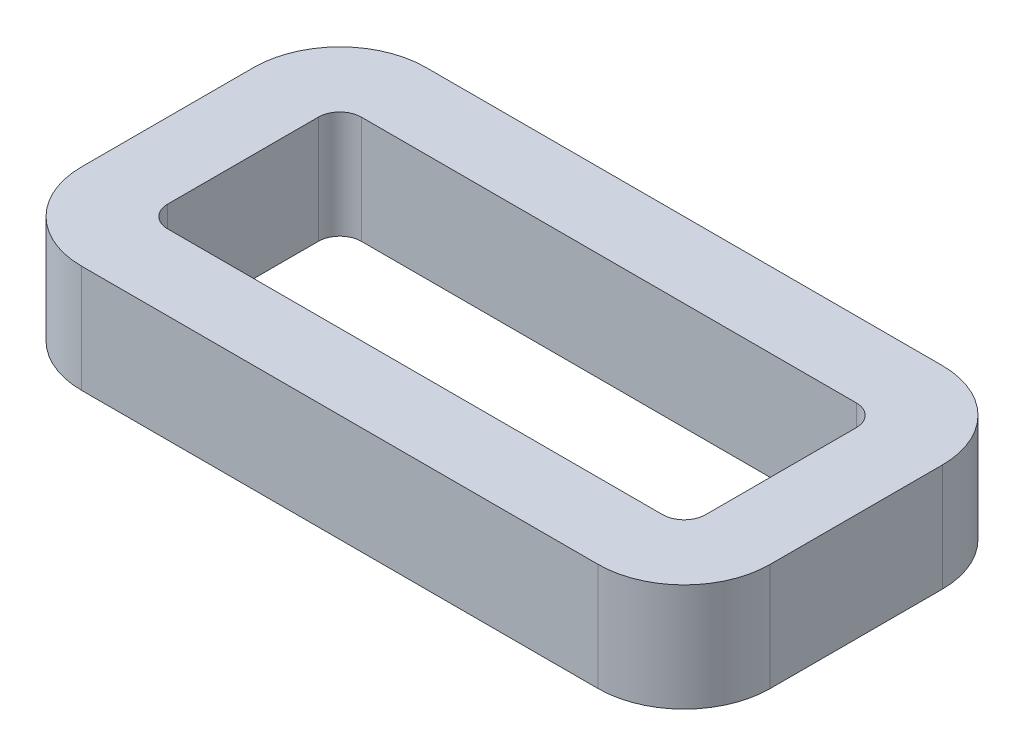
SolidWorks part; units mm, degrees
ref_plane "Alzado" through (0, 0, 0) normal (0, 0, 1) x (1, 0, 0)
ref_plane "Planta" through (0, 0, 0) normal (0, 1, 0) x (1, 0, 0)
ref_plane "Vista lateral" through (0, 0, 0) normal (1, 0, 0) x (0, 0, -1)
sketch "Croquis1" plane through (0, 0, 0) normal (0, 1, 0) x (1, 0, 0)
  line L0 (8, 0) -> (8, 1.75) construction
  line L1 (2, 0) -> (14, 0)
  line L2 (0, 2) -> (0, 6)
  line L3 (2, 8) -> (14, 8)
  line L4 (16, 2) -> (16, 6)
  line L5 (0, 4) -> (1.75, 4) construction
  line L6 (8, 8) -> (8, 6.25) construction
  line L7 (16, 4) -> (14.25, 4) construction
  line L8 (8, 6.25) -> (1.75, 6.25) construction
  line L9 (1.75, 5.75) -> (1.75, 2.25)
  line L10 (2.25, 1.75) -> (13.75, 1.75)
  line L11 (14.25, 2.25) -> (14.25, 5.75)
  line L12 (14.25, 6.25) -> (8, 6.25) construction
  line L13 (2.25, 6.25) -> (13.75, 6.25)
  arc A0 (1.75, 5.75) -> (2.25, 6.25) centre (2.25, 5.75) cw
  arc A1 (13.75, 6.25) -> (14.25, 5.75) centre (13.75, 5.75) cw
  arc A2 (14.25, 2.25) -> (13.75, 1.75) centre (13.75, 2.25) cw
  arc A3 (1.75, 2.25) -> (2.25, 1.75) centre (2.25, 2.25) ccw
  arc A4 (0, 6) -> (2, 8) centre (2, 6) cw
  arc A5 (2, 0) -> (0, 2) centre (2, 2) cw
  arc A6 (14, 0) -> (16, 2) centre (14, 2) ccw
  arc A7 (14, 8) -> (16, 6) centre (14, 6) cw
  point P29 (0, 8)
  point P32 (0, 0)
  point P35 (16, 0)
  dimension "D7" = 0.5
  dimension "D8" = 2
  dimension "D1" = 8
  dimension "D2" = 16
  dimension "D3" = 1.75
  dimension "D4" = 1.75
  dimension "D5" = 1.75
  dimension "D6" = 1.75
extrude "Saliente-Extruir2" add sketch "Croquis1" along normal blind 1.25 and the other way blind 1.25
